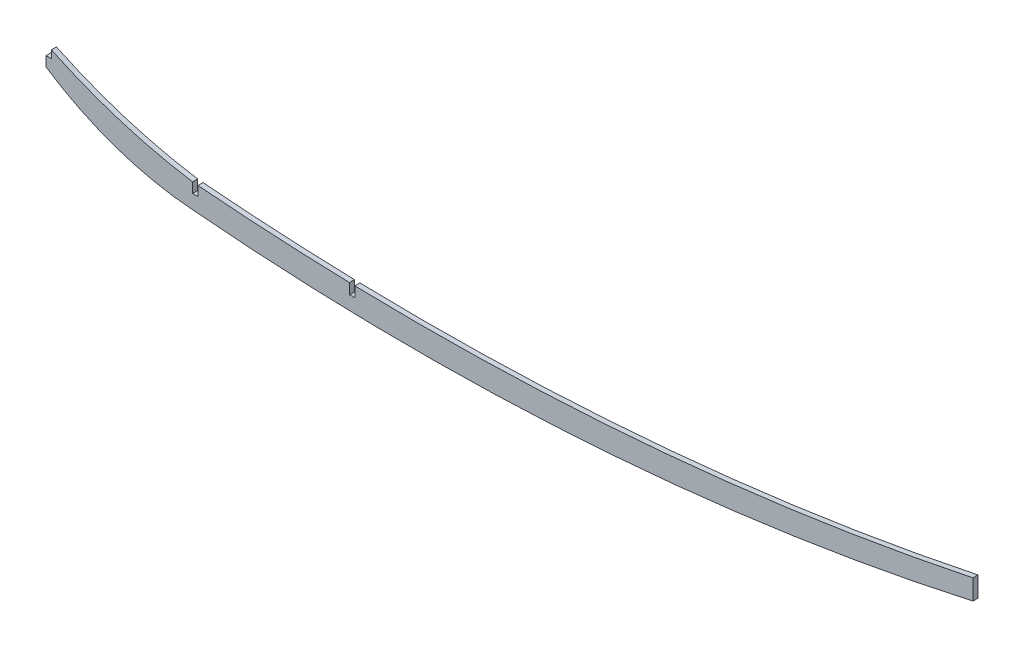
SolidWorks part; units mm, degrees
material "Balsa"
ref_plane "Front Plane" through (0, 0, 0) normal (0, 0, 1) x (1, 0, 0)
ref_plane "Top Plane" through (0, 0, 0) normal (0, 1, 0) x (1, 0, 0)
ref_plane "Right Plane" through (0, 0, 0) normal (1, 0, 0) x (0, 0, -1)
sketch "Sketch1" plane through (0, 0, 0) normal (0, 0, 1) x (1, 0, 0)
  line L3 (0, -97.563) -> (0, -84.863)
  line L4 (583.5225, -97.0036) -> (583.5225, -84.3036)
  arc A6 (0, -97.563) -> (92.3925, -129.289) centre (106.9176, 63.4069) ccw
  arc A10 (92.3925, -129.289) -> (583.5225, -97.0036) centre (233.5795, 1474.6667) ccw
  arc A17 (0, -84.863) -> (92.3925, -114.049) centre (142.0237, 203.9001) ccw
  arc A19 (92.3925, -114.049) -> (583.5225, -84.3036) centre (236.5524, 1575.136) ccw
  dimension "D1" = 193.2426
  dimension "D5" = 1610.1576
  dimension "D6" = 583.5225
  dimension "D4" = 31.726
  dimension "D10" = 15.24
  dimension "D11" = 321.7994
  dimension "D12" = 1695.3253
  dimension "D2" = 97.563
  dimension "D3" = 92.3925
  dimension "D7" = 97.0036
  dimension "D8" = 12.7
  dimension "D9" = 12.7
extrude "Boss-Extrude1" add sketch "Sketch1" along normal mid plane 3.175 contours A19 A17 L3 A6 A10 L4 region at (5.8576, -91.213, 0)
sketch "Sketch2" plane through (0, 0, 1.5875) normal (0, 0, 1) x (1, 0, 0)
  line L0 (0, 0) -> (0, -84.863) construction
  line L1 (0, 0) -> (93.98, 0) construction
  line L2 (0, -84.863) -> (3.3782, -84.863)
  line L3 (0, -84.863) -> (0, -91.34)
  line L4 (0, -91.34) -> (3.3782, -91.34)
  line L5 (3.3782, -84.863) -> (3.3782, -91.34)
  line L6 (93.98, 0) -> (93.98, -120.3396) construction
  line L9 (92.2909, -120.4158) -> (95.6691, -120.4158)
  line L10 (92.2909, -120.4158) -> (92.2909, -107.7158)
  line L11 (95.6691, -120.4158) -> (95.6691, -107.7158)
  line L12 (92.2909, -107.7158) -> (95.6691, -107.7158)
  line L14 (191.1554, -126.1955) -> (194.5328, -126.1248)
  line L21 (192.8425, -126.084) -> (190.203, 0) construction
  line L23 (93.98, 0) -> (241.3865, 0) construction
  line L25 (191.1554, -126.1955) -> (190.8896, -113.4983)
  line L26 (194.5328, -126.1248) -> (194.267, -113.4276)
  line L27 (190.8896, -113.4983) -> (194.267, -113.4276)
  point P3 (93.98, -107.7158)
  point P11 (192.5783, -113.463)
  point P14 (192.8441, -126.1602)
  dimension "D1" = 84.863
  dimension "D2" = 6.477
  dimension "D3" = 3.3782
  dimension "D4" = 93.98
  dimension "D5" = 120.3396
  dimension "D6" = 0.0762
  dimension "D7" = 3.3782
  dimension "D8" = 91.199
  dimension "D9" = 190.203
  dimension "D10" = 126.1116
  dimension "D11" = 0.0762
  dimension "D12" = 3.3782
  dimension "D13" = 12.7
  dimension "D14" = 12.7
extrude "Cut-Extrude1" cut sketch "Sketch2" against normal through all
equation "\"slotwidth\"=0.197118"
